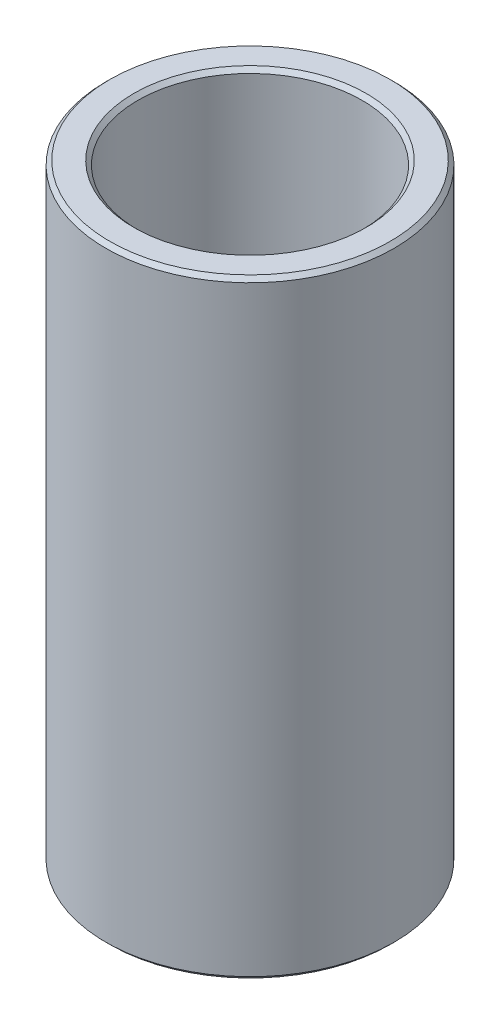
SolidWorks part; units mm, degrees
material "Pure Silver"
ref_plane "Front Plane" through (0, 0, 0) normal (0, 0, 1) x (1, 0, 0)
ref_plane "Top Plane" through (0, 0, 0) normal (0, 1, 0) x (1, 0, 0)
ref_plane "Right Plane" through (0, 0, 0) normal (1, 0, 0) x (0, 0, -1)
sketch "Sketch1" plane through (0, 0, 0) normal (0, 0, 1) x (1, 0, 0)
  line L0 (0, -587.1511) -> (0, 28770.4063) construction
  line L1 (2, 0) -> (2, 1)
  line L2 (2, 1) -> (5, 4)
  line L3 (5, 4) -> (7, 4)
  line L4 (7, 4) -> (7, 38)
  line L5 (7, 38) -> (9, 38)
  line L6 (9, 38) -> (9, 0)
  line L7 (9, 0) -> (2, 0)
  dimension "D1" = 18
  dimension "D2" = 38
  dimension "D3" = 2
  dimension "D4" = 4
  dimension "D5" = 4
  dimension "D6" = 45
  dimension "D7" = 10
revolve "Revolve1" add sketch "Sketch1" angle 360 about L0
chamfer "Chamfer1" distance 0.25 angle 45 4 edges at (9, 38, 0) (7, 38, 0) (9, 0, 0) (2, 0, 0)
